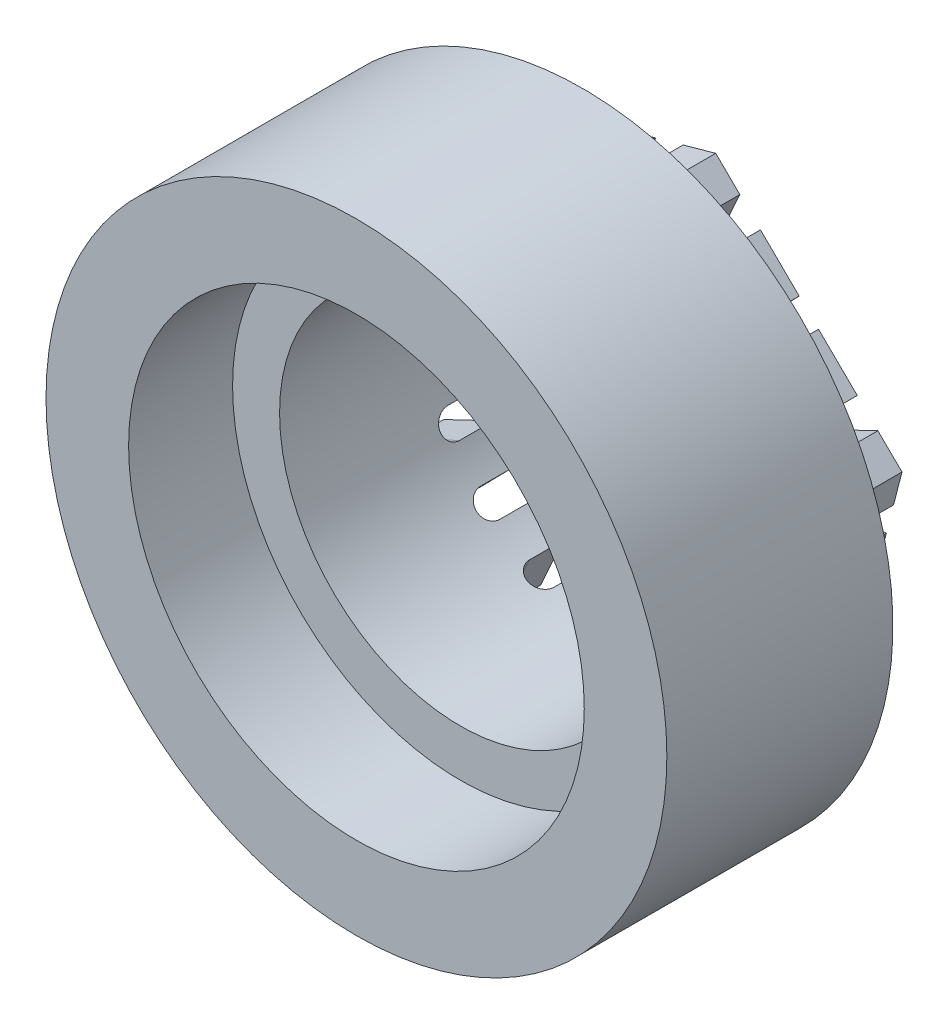
SolidWorks part; units mm, degrees
material "AISI Type 316L stainless steel"
ref_plane "Front Plane" through (0, 0, 0) normal (0, 0, 1) x (1, 0, 0)
ref_plane "Top Plane" through (0, 0, 0) normal (0, 1, 0) x (1, 0, 0)
ref_plane "Right Plane" through (0, 0, 0) normal (1, 0, 0) x (0, 0, -1)
sketch "Sketch1" plane through (0, 0, 0) normal (0, 0, 1) x (1, 0, 0)
  circle A0 centre (0, 0) radius 21.7995
  dimension "D1" = 43.5991
extrude "Boss-Extrude1" add sketch "Sketch1" along normal blind 20.6502
sketch "Sketch2" plane through (0, 0, 20.6502) normal (0, 0, 1) x (1, 0, 0)
  circle A0 centre (0, 0) radius 12.7
  dimension "D1" = 25.4
extrude "Cut-Extrude1" cut sketch "Sketch2" against normal blind 20.6502
sketch "Sketch3" plane through (0, 0, 20.6502) normal (0, 0, 1) x (1, 0, 0)
  circle A0 centre (0, 0) radius 16
  dimension "D1" = 32
extrude "Cut-Extrude2" cut sketch "Sketch3" against normal blind 7.3025
sketch "Sketch4" plane through (0, 0, 0) normal (0, 0, -1) x (-1, 0, 0)
  line L1 (17.6618, -4.9073) -> (13.0808, 12.8419)
  line L2 (13.0808, 12.8419) -> (-4.581, 17.7492)
  line L3 (-4.581, 17.7492) -> (-17.6618, 4.9073)
  line L4 (-17.6618, 4.9073) -> (-13.0808, -12.8419)
  line L5 (-13.0808, -12.8419) -> (4.581, -17.7492)
  line L6 (4.581, -17.7492) -> (17.6618, -4.9073)
  circle A1 centre (0, 0) radius 15.875 construction
  dimension "D1" = 31.75
extrude "Cut-Extrude3" cut sketch "Sketch4" against normal blind 4.7752 flip side to cut
sketch "Sketch5" plane through (-15.3713, 3.9673, 0) normal (-0.9683, 0.2499, 0) x (0, 0, 1)
  line L0 (0, 0) -> (4.7752, 0) construction
  line L1 (4.7752, -9.1654) -> (4.7752, 9.1654) construction
  line L2 (2.3876, 0.9525) -> (0, 0.9525)
  line L3 (0, -9.1654) -> (0, 9.1654) construction
  line L4 (0, 0.9525) -> (0, -0.9525)
  line L5 (0, -0.9525) -> (2.3876, -0.9525)
  arc A1 (2.3876, 0.9525) -> (2.3876, -0.9525) centre (2.3876, 0) cw
extrude "Cut-Extrude4" cut sketch "Sketch5" against normal blind 9.8552 and the other way blind 9.8552
pattern_circular "CirPattern1" count 18 over 360 about axis through (0, 0, 13.3477) along (0, 0, 1) of "Cut-Extrude4" reverse direction yes
